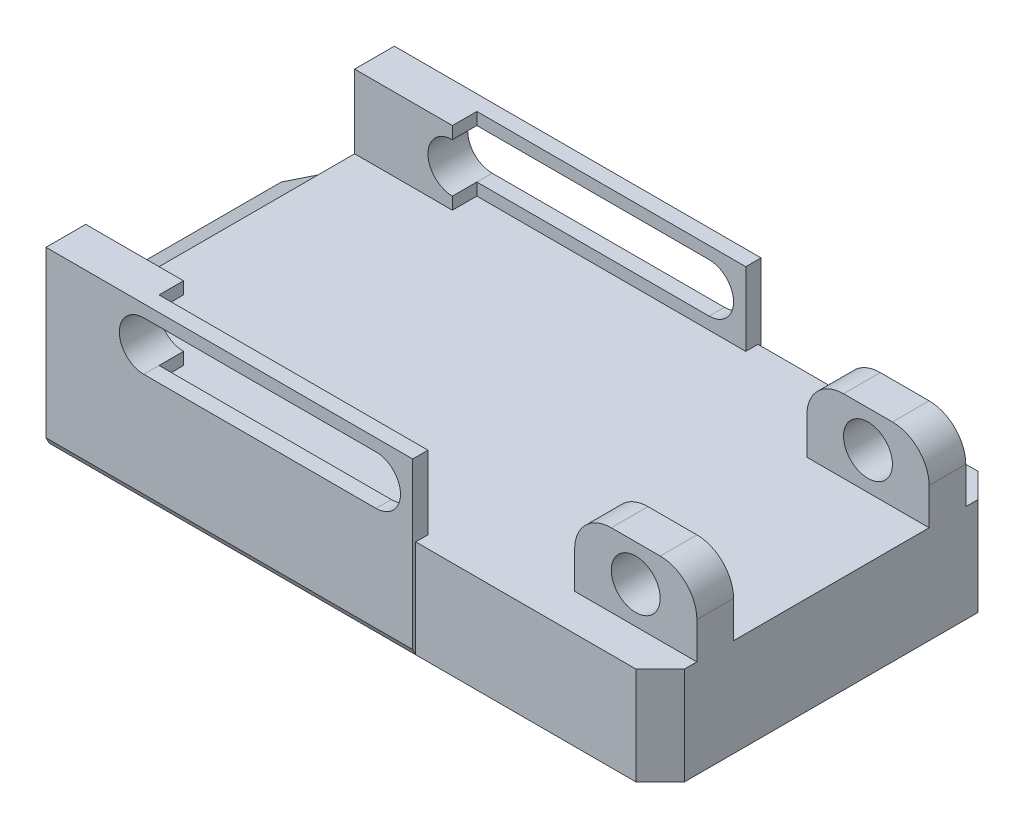
SolidWorks part; units mm, degrees
ref_plane "Front Plane" through (0, 0, 0) normal (0, 0, 1) x (1, 0, 0)
ref_plane "Top Plane" through (0, 0, 0) normal (0, 1, 0) x (1, 0, 0)
ref_plane "Right Plane" through (0, 0, 0) normal (1, 0, 0) x (0, 0, -1)
sketch "Sketch1" plane through (0, 0, 0) normal (0, 1, 0) x (1, 0, 0)
  line L1 (-125, -70) -> (125, -70)
  line L2 (-125, -70) -> (-125, 70)
  line L3 (-125, 70) -> (125, 70)
  line L4 (125, -70) -> (125, 70)
  line L5 (-125, -70) -> (125, 70) construction
  line L6 (-125, 70) -> (125, -70) construction
  point P0 (0, 0)
extrude "Boss-Extrude1" add sketch "Sketch1" along normal blind 10
sketch "Sketch2" plane through (0, 10, 0) normal (0, 1, 0) x (1, 0, 0)
  line L0 (125, 0) -> (125, 20)
  line L1 (125, 70) -> (75, 70)
  line L2 (125, 70) -> (125, 50)
  line L3 (125, 50) -> (75, 50)
  line L4 (75, 70) -> (75, 50)
  line L5 (125, -70) -> (75, -70)
  line L6 (125, -70) -> (125, -50)
  line L7 (125, -50) -> (75, -50)
  line L8 (75, -70) -> (75, -50)
  line L9 (125, -70) -> (125, 70) construction
  line L10 (125, 20) -> (105, 20)
  line L11 (105, 20) -> (105, -20)
  line L12 (105, -20) -> (125, -20)
  line L13 (125, -20) -> (125, 0)
  line L15 (-125, 70) -> (-125, -70) construction
  line L16 (-125, -45) -> (25, -45)
  line L17 (25, -45) -> (25, -25)
  line L18 (25, -25) -> (-125, -25)
  line L19 (-125, -25) -> (-125, -45)
  line L21 (-125, 25) -> (-125, 45)
  line L22 (25, 25) -> (-125, 25)
  line L23 (25, 45) -> (25, 25)
  line L24 (-125, 45) -> (25, 45)
  line L25 (-125, 70) -> (-125, 45)
  line M15 (125, -70) -> (125, 70)
  line M16 (125, 70) -> (-125, 70)
  line M17 (-125, 70) -> (-125, -70)
  line M18 (-125, -70) -> (125, -70)
extrude "Boss-Extrude2" add sketch "Sketch2" along normal blind 30 contours L24 L22 L23 M17 | L17 L18 L16 M17 | L11 L12 L10 M15 | L4 L3 M16 M15 | L8 L7 M18 M15 region at (115, 10, 0) region at (100, 10, -60) region at (100, 10, 60) region at (-50, 10, -35) region at (-50, 10, 35)
sketch "Sketch3" plane through (0, 0, 45) normal (0, 0, 1) x (1, 0, 0)
  line L0 (25, 25) -> (10, 25) construction
  line L1 (25, 40) -> (25, 10) construction
  line L2 (-125, 25) -> (-110, 25) construction
  line L3 (-125, 40) -> (-125, 10) construction
  line L4 (10, 35) -> (-110, 35)
  line L5 (10, 15) -> (-110, 15)
  arc A0 (10, 15) -> (10, 35) centre (10, 25) ccw
  arc A1 (-110, 35) -> (-110, 15) centre (-110, 25) ccw
extrude "Cut-Extrude1" cut sketch "Sketch3" against normal blind 120
sketch "Sketch4" plane through (0, 0, 70) normal (0, 0, 1) x (1, 0, 0)
  line L0 (75, 10) -> (125, 40) construction
  circle A0 centre (100, 25) radius 10
extrude "Cut-Extrude2" cut sketch "Sketch4" against normal blind 150
sketch "Sketch6" plane through (0, 10, 0) normal (0, 1, 0) x (1, 0, 0)
  line L0 (125, 20) -> (105, 20) construction
  line L1 (115, 20) -> (105, 20)
  line L2 (115, 20) -> (115, -20)
  line L3 (115, -20) -> (105, -20)
  line L4 (105, 20) -> (105, -20)
extrude "Cut-Extrude4" cut sketch "Sketch6" along normal blind 150
sketch "Sketch7" plane through (125, 0, 0) normal (1, 0, 0) x (0, 0, -1)
  line L0 (-20, 10) -> (20, 40) construction
  circle A0 centre (0, 25) radius 10
extrude "Cut-Extrude5" cut sketch "Sketch7" against normal blind 150
fillet "Fillet2" radius 10 2 edges at (120, 40, 20) (120, 40, -20)
fillet "Fillet3" radius 10 4 edges at (75, 40, 60) (125, 40, 60) (75, 40, -60) (125, 40, -60)
sketch "Sketch13" plane through (0, 10, 0) normal (0, 1, 0) x (1, 0, 0)
  line L0 (75, 70) -> (75, 50) construction
  line L1 (75, 60) -> (125, 60)
  line L2 (75, 60) -> (75, 35)
  line L3 (75, 35) -> (125, 35)
  line L4 (125, 60) -> (125, 35)
  line L5 (125, 20) -> (125, 50) construction
  line L6 (75, -70) -> (75, -50) construction
  line L7 (75, -60) -> (125, -60)
  line L8 (75, -60) -> (75, -37.7557)
  line L9 (75, -37.7557) -> (125, -37.7557)
  line L10 (125, -60) -> (125, -37.7557)
  line L11 (125, -50) -> (125, -20) construction
extrude "Cut-Extrude6" cut sketch "Sketch13" along normal blind 40
sketch "Sketch14" plane through (0, 0, 70) normal (0, 0, 1) x (1, 0, 0)
  line L0 (10, 35) -> (-85, 35)
  line L1 (-125, 40) -> (25, 40)
  line L2 (-125, 40) -> (-125, 10)
  line L3 (-125, 10) -> (25, 10)
  line L4 (25, 40) -> (25, 10)
  line L5 (-110, 25) -> (-85, 25) construction
  line L6 (-85, 15) -> (10, 15)
  arc A0 (10, 15) -> (10, 35) centre (10, 25) ccw
  arc A2 (-85, 35) -> (-85, 15) centre (-85, 25) ccw
extrude "Boss-Extrude3" add sketch "Sketch14" against normal blind 10
sketch "Sketch16" plane through (0, 0, -70) normal (0, 0, -1) x (-1, 0, 0)
  line L0 (85, 35) -> (-10, 35)
  line L1 (-25, 10) -> (125, 10)
  line L2 (-25, 10) -> (-25, 40)
  line L3 (-25, 40) -> (125, 40)
  line L4 (125, 10) -> (125, 40)
  line L6 (-10, 15) -> (85, 15)
  arc A0 (-10, 35) -> (-10, 15) centre (-10, 25) ccw
  arc A1 (85, 15) -> (85, 35) centre (85, 25) ccw
extrude "Boss-Extrude4" add sketch "Sketch16" against normal blind 10
sketch "Sketch17" plane through (125, 0, 0) normal (1, 0, 0) x (0, 0, -1)
  line L0 (45, 10) -> (25, 10) construction
  line L1 (25, 40) -> (35, 40)
  line L2 (25, 40) -> (25, 10)
  line L3 (25, 10) -> (35, 10)
  line L4 (35, 40) -> (35, 10)
  line L5 (-45, 10) -> (-25, 10) construction
  line L6 (-25, 40) -> (-35, 40)
  line L7 (-25, 40) -> (-25, 10)
  line L8 (-25, 10) -> (-35, 10)
  line L9 (-35, 40) -> (-35, 10)
extrude "Boss-Extrude5" add sketch "Sketch17" against normal blind 50
sketch "Sketch18" plane through (0, 0, -70) normal (0, 0, -1) x (-1, 0, 0)
  circle A0 centre (-100, 25) radius 10
extrude "Cut-Extrude7" cut sketch "Sketch18" against normal blind 150
sketch "Sketch19" plane through (0, 10, 0) normal (0, 1, 0) x (1, 0, 0)
  line L0 (-125, -45) -> (-125, -60) construction
  line L1 (-125, -49.7072) -> (38.5706, -49.7072)
  line L2 (-125, -49.7072) -> (-125, 49.9788)
  line L3 (-125, 49.9788) -> (38.5706, 49.9788)
  line L4 (38.5706, -49.7072) -> (38.5706, 49.9788)
  line L6 (67.0911, 49.9788) -> (131.1943, 49.9788)
  line L7 (67.0911, 49.9788) -> (67.0911, 79.8574)
  line L8 (67.0911, 79.8574) -> (131.1943, 79.8574)
  line L9 (131.1943, 49.9788) -> (131.1943, 79.8574)
  line L10 (67.0911, -47.5342) -> (153.1958, -47.5342)
  line L11 (67.0911, -47.5342) -> (67.0911, -86.9196)
  line L12 (67.0911, -86.9196) -> (153.1958, -86.9196)
  line L13 (153.1958, -47.5342) -> (153.1958, -86.9196)
  line L14 (112.888, -22.1619) -> (135.5758, -22.1619)
  line L15 (112.888, -22.1619) -> (112.888, 23.2138)
  line L16 (112.888, 23.2138) -> (135.5758, 23.2138)
  line L17 (135.5758, -22.1619) -> (135.5758, 23.2138)
extrude "Cut-Extrude8" cut sketch "Sketch19" along normal blind 150
sketch "Sketch20" plane through (0, 0, 0) normal (0, -1, 0) x (1, 0, 0)
  line L0 (-125, 40) -> (-125, 70)
  line L1 (-125, -70) -> (125, -70)
  line L2 (-125, -70) -> (-125, -40)
  line L3 (-125, 70) -> (125, 70)
  line L4 (125, -70) -> (125, 70)
  line L5 (-125, -70) -> (125, 70) construction
  line L6 (-125, 70) -> (125, -70) construction
  line L7 (-120, -65) -> (120, -65)
  line L8 (-120, -65) -> (-120, -40)
  line L9 (-120, 65) -> (120, 65)
  line L10 (120, -65) -> (120, 65)
  line L11 (-120, -65) -> (120, 65) construction
  line L12 (-120, 65) -> (120, -65) construction
  line L13 (-120, 40) -> (-125, 40)
  line L15 (-120, -40) -> (-125, -40)
  line L19 (-120, 40) -> (-120, 65)
  point P0 (0, 0)
  point P7 (0, 0)
  point P12 (-125, 0)
extrude "Boss-Extrude6" add sketch "Sketch20" along normal blind 30
sketch "Sketch21" plane through (0, 0, 35) normal (0, 0, 1) x (1, 0, 0)
  line L1 (75, 10) -> (125, 10)
  line L2 (75, 10) -> (75, 40)
  line L3 (75, 40) -> (125, 40)
  line L4 (125, 10) -> (125, 40)
  circle A0 centre (100, 25) radius 10
extrude "Boss-Extrude8" add sketch "Sketch21" along normal blind 20
sketch "Sketch22" plane through (0, 0, -35) normal (0, 0, -1) x (-1, 0, 0)
  line L1 (-125, 10) -> (-75, 10)
  line L2 (-125, 10) -> (-125, 40)
  line L3 (-125, 40) -> (-75, 40)
  line L4 (-75, 10) -> (-75, 40)
  circle A0 centre (-100, 25) radius 10
extrude "Boss-Extrude9" add sketch "Sketch22" along normal blind 20
sketch "Sketch23" plane through (0, 0, 70) normal (0, 0, 1) x (1, 0, 0)
  line L0 (10, 35) -> (-85, 35)
  line L1 (25, 10) -> (-125, 10)
  line L2 (25, 10) -> (25, 40)
  line L3 (25, 40) -> (-125, 40)
  line L4 (-125, 10) -> (-125, 40)
  line L6 (-85, 15) -> (10, 15)
  arc A0 (10, 15) -> (10, 35) centre (10, 25) ccw
  arc A1 (-85, 35) -> (-85, 15) centre (-85, 25) ccw
extrude "Boss-Extrude10" add sketch "Sketch23" along normal blind 20
sketch "Sketch24" plane through (0, 0, -70) normal (0, 0, -1) x (-1, 0, 0)
  line L0 (-10, 35) -> (85, 35)
  line L1 (-25, 10) -> (125, 10)
  line L2 (-25, 10) -> (-25, 40)
  line L3 (-25, 40) -> (125, 40)
  line L4 (125, 10) -> (125, 40)
  line L6 (85, 15) -> (-10, 15)
  arc A0 (-10, 35) -> (-10, 15) centre (-10, 25) ccw
  arc A1 (85, 15) -> (85, 35) centre (85, 25) ccw
extrude "Boss-Extrude11" add sketch "Sketch24" along normal blind 20
sketch "Sketch26" plane through (25, 0, 0) normal (1, 0, 0) x (0, 0, -1)
  line L0 (70, -30) -> (90, 10)
  line L1 (90, 10) -> (70, 10)
  line L2 (70, 10) -> (70, -30)
  line L3 (-90, 10) -> (-70, 10)
  line L4 (-70, 10) -> (-70, -30)
  line L5 (-70, -30) -> (-90, 10)
extrude "Boss-Extrude12" add sketch "Sketch26" against normal up to surface (150 mm away) up to face at (-125, 6.25, 0)
sketch "Sketch27" plane through (0, 10, 0) normal (0, 1, 0) x (1, 0, 0)
  line L5 (25, 60) -> (25, 70) construction
  line L6 (-125, 60) -> (25, 60)
  line L7 (-125, 60) -> (-125, 65)
  line L8 (-125, 65) -> (25, 65)
  line L9 (25, 60) -> (25, 65)
  line L10 (25, -60) -> (25, -70) construction
  line L11 (-125, -60) -> (25, -60)
  line L12 (-125, -60) -> (-125, -65)
  line L13 (-125, -65) -> (25, -65)
  line L14 (25, -60) -> (25, -65)
extrude "Cut-Extrude10" cut sketch "Sketch27" along normal blind 40
sketch "Sketch28" plane through (-125, 0, 0) normal (-1, 0, 0) x (0, 0, 1)
  line L0 (-65, 40) -> (-90, 40) construction
  line L1 (-77.5, 40) -> (-104.9033, 40)
  line L2 (-77.5, 40) -> (-77.5, -34.4267)
  line L3 (-77.5, -34.4267) -> (-104.9033, -34.4267)
  line L4 (-104.9033, 40) -> (-104.9033, -34.4267)
  line L5 (65, 40) -> (90, 40) construction
  line L6 (77.5, 40) -> (100.9137, 40)
  line L7 (77.5, 40) -> (77.5, -38.651)
  line L8 (77.5, -38.651) -> (100.9137, -38.651)
  line L9 (100.9137, 40) -> (100.9137, -38.651)
extrude "Cut-Extrude11" cut sketch "Sketch28" against normal up to surface (150 mm away) up to face at (25, 13.3333, -75)
sketch "Sketch29" plane through (-125, 0, 0) normal (-1, 0, 0) x (0, 0, 1)
  line L0 (55, 10) -> (25, 10) construction
  line L1 (-40, 0) -> (40, 0)
  line L2 (-40, 0) -> (-40, 10)
  line L3 (-40, 10) -> (40, 10)
  line L4 (40, 0) -> (40, 10)
extrude "Boss-Extrude13" add sketch "Sketch29" along normal blind 15
sketch "Sketch31" plane through (0, 0, 40) normal (0, 0, 1) x (1, 0, 0)
  line L0 (-140, 0) -> (-125, 10)
  line L1 (-125, 10) -> (-140, 10)
  line L2 (-140, 10) -> (-140, 0)
extrude "Cut-Extrude12" cut sketch "Sketch31" against normal up to surface (80 mm away) up to face at (-132.5, 5, -40)
sketch "Sketch40" plane through (0, 40, 0) normal (0, 1, 0) x (1, 0, 0)
  line L0 (25, 65) -> (25, 77.5) construction
  line L1 (25, 71.25) -> (-125, 71.25)
  line L2 (25, 71.25) -> (25, 77.5)
  line L3 (25, 77.5) -> (-125, 77.5)
  line L4 (-125, 71.25) -> (-125, 77.5)
  line L5 (25, -65) -> (25, -77.5) construction
  line L6 (25, -71.25) -> (-125, -71.25)
  line L7 (25, -71.25) -> (25, -77.5)
  line L8 (25, -77.5) -> (-125, -77.5)
  line L9 (-125, -71.25) -> (-125, -77.5)
extrude "Cut-Extrude16" cut sketch "Sketch40" against normal blind 200
chamfer "Chamfer1" distance 10 angle 45 2 edges at (125, -10, -70) (125, -10, 70)
fillet "Fillet6" radius 15 4 edges at (125, 40, 40) (75, 40, 40) (125, 40, -40) (75, 40, -40)
chamfer "Chamfer2" distance 20 angle 45 2 edges at (-122.5, -30, 40) (-122.5, -30, -40)
fillet "Fillet7" radius 15 2 edges at (120, -15, -65) (120, -15, 65)
sketch "Sketch41" plane through (75, 0, 0) normal (-1, 0, 0) x (0, 0, 1)
  line L6 (-55, 40) -> (-25, 40) construction
  line L7 (-40, 40) -> (40, 40)
  line L8 (-40, 40) -> (-40, 10)
  line L9 (-40, 10) -> (40, 10)
  line L10 (40, 40) -> (40, 10)
  line L11 (55, 10) -> (25, 10) construction
extrude "Cut-Extrude18" cut sketch "Sketch41" against normal blind 200
sketch "Sketch42" plane through (0, 0, -65) normal (0, 0, 1) x (1, 0, 0)
  line L0 (-85, 35) -> (-85, 40)
  line L1 (-125, 10) -> (-85, 10)
  line L2 (-125, 10) -> (-125, 40)
  line L3 (-125, 40) -> (-85, 40)
  line L4 (-85, 10) -> (-85, 15)
  arc A0 (-85, 35) -> (-85, 15) centre (-85, 25) ccw
extrude "Boss-Extrude16" add sketch "Sketch42" along normal blind 10
sketch "Sketch43" plane through (0, 0, 65) normal (0, 0, -1) x (-1, 0, 0)
  line L0 (85, 35) -> (85, 40)
  line L1 (85, 10) -> (125, 10)
  line L2 (85, 10) -> (85, 15)
  line L3 (85, 40) -> (125, 40)
  line L4 (125, 10) -> (125, 40)
  arc A0 (85, 15) -> (85, 35) centre (85, 25) ccw
extrude "Boss-Extrude17" add sketch "Sketch43" along normal blind 10
